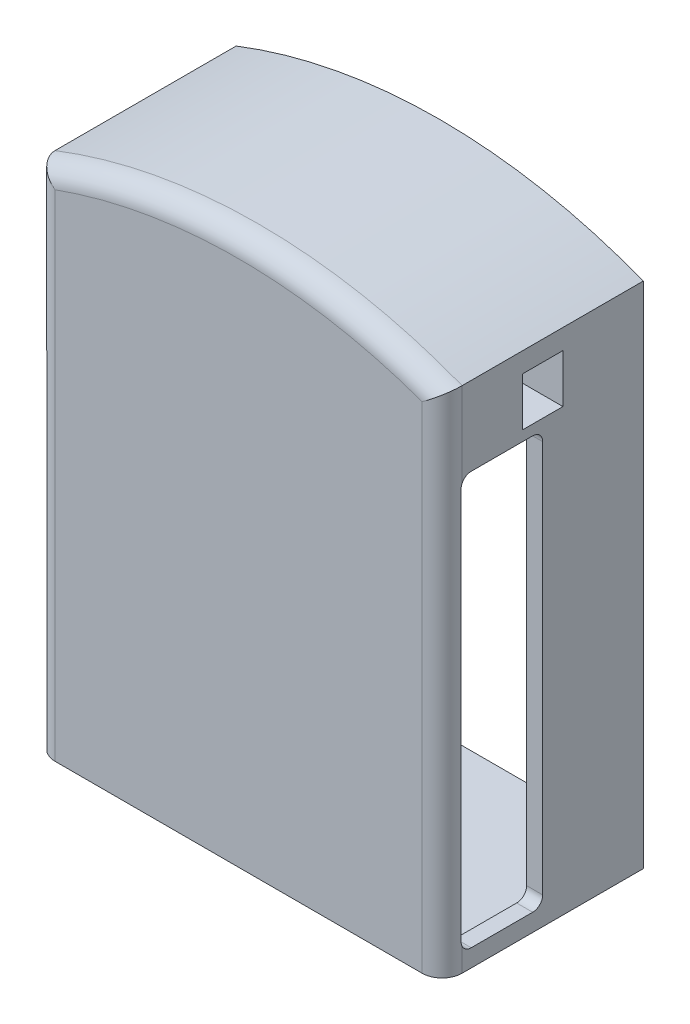
SolidWorks part; units mm, degrees
ref_plane "Front Plane" through (0, 0, 0) normal (0, 0, 1) x (1, 0, 0)
ref_plane "Top Plane" through (0, 0, 0) normal (0, 1, 0) x (1, 0, 0)
ref_plane "Right Plane" through (0, 0, 0) normal (1, 0, 0) x (0, 0, -1)
sketch "Sketch1" plane through (0, 0, 0) normal (0, 1, 0) x (1, 0, 0)
  line L1 (-50.8, -25.1) -> (50.8, -25.1)
  line L2 (-50.8, -25.1) -> (-50.8, 25.1)
  line L3 (-50.8, 25.1) -> (50.8, 25.1)
  line L4 (50.8, -25.1) -> (50.8, 25.1)
  point P4 (0, 25.1)
  point P6 (50.8, 0)
  dimension "D1" = 50.2
  dimension "D2" = 101.6
extrude "Boss-Extrude1" add sketch "Sketch1" along normal blind 127
shell "Shell2" thickness 4
sketch "Sketch2" plane through (0, 0, 21.1) normal (0, 0, -1) x (-1, 0, 0)
  line L2 (40.0386, 104.4679) -> (-40.0386, 104.4679)
  line L3 (41.5386, 12.0015) -> (41.5386, 105.9679)
  line L6 (-40.0386, 13.5015) -> (-40.0386, 104.4679)
  line L8 (40.0386, 13.5015) -> (40.0386, 104.4679)
  line L9 (-41.5386, 12.0015) -> (-41.5386, 105.9679)
  line L10 (-41.5386, 12.0015) -> (-41.5386, 4)
  line L11 (-46.8, 4) -> (46.8, 4) construction
  line L12 (-40.0386, 13.5015) -> (-40.0386, 4)
  line L13 (40.0386, 13.5015) -> (40.0386, 4)
  line L14 (46.8, 4) -> (-46.8, 4) construction
  line L15 (41.5386, 12.0015) -> (41.5386, 4)
  line L16 (41.5386, 4) -> (40.0386, 4)
  line L17 (-41.5386, 4) -> (-40.0386, 4)
  line L18 (-41.5386, 105.9679) -> (41.5386, 105.9679)
  line L19 (-41.5386, 12.0015) -> (41.5386, 12.0015) construction
  line L20 (-40.0386, 13.5015) -> (40.0386, 13.5015) construction
  line L22 (-41.5386, 12.0015) -> (-41.5386, 115.4679) construction
  line L23 (-40.0386, 13.5015) -> (-40.0386, 113.9679) construction
  line L24 (-40.0386, 113.9679) -> (40.0386, 113.9679) construction
  line L25 (-41.5386, 115.4679) -> (41.5386, 115.4679) construction
  line L26 (41.5386, 12.0015) -> (41.5386, 115.4679) construction
  line L27 (40.0386, 13.5015) -> (40.0386, 113.9679) construction
  point P9 (0, 63.5)
  point P12 (0, 63.5)
  point P15 (0, 113.9679)
  point P18 (-40.0386, 63.7347)
  dimension "D3" = 1.5
  dimension "D1" = 1.5
extrude "Boss-Extrude2" add sketch "Sketch2" along normal blind 2
fillet "Fillet1" radius 5 2 edges at (50.8, 63.5, 25.1) (-50.8, 63.5, 25.1)
sketch "Sketch4" plane through (50.8, 0, 0) normal (1, 0, 0) x (0, 0, -1)
  line L5 (-20.3461, 4.3823) -> (0, 4.3823)
  line L6 (-20.3461, 4.3823) -> (-20.3461, 107.3452)
  line L7 (-20.3461, 107.3452) -> (0, 107.3452)
  line L8 (0, 4.3823) -> (0, 107.3452)
extrude "Cut-Extrude2" cut sketch "Sketch4" against normal blind 7
fillet "Fillet2" radius 2.5 4 edges at (48.797, 4.3823, 20.3461) (48.8, 4.3823, 0) (48.8, 107.3452, 0) (48.797, 107.3452, 20.3461)
mirror "Mirror1" about plane through (0, 0, 0) normal (1, 0, 0) of "Fillet2", "Cut-Extrude2"
sketch "Sketch5" plane through (0, 0, 25.1) normal (0, 0, 1) x (1, 0, 0)
  line L0 (-50.8, 127) -> (50.8, 127)
  arc A0 (-50.8, 127) -> (50.8, 127) centre (0, -3.4583) cw
  dimension "D1" = 140
extrude "Boss-Extrude4" add sketch "Sketch5" against normal blind 50.2
fillet "Fillet4" radius 5 1 edges at (0, 136.5417, 25.1)
sketch "Sketch6" plane through (46.8, 0, 0) normal (-1, 0, 0) x (0, 0, 1)
  line L0 (-25.1, 120.6928) -> (25.1, 120.6928) construction
  line L1 (0, -55.88) -> (0, 55.88) construction
  line L2 (25.1, 0) -> (25.1, 123.5353) construction
  line L3 (21.1, 123) -> (-25.1, 123) construction
  line L4 (-5.05, 122) -> (5.05, 122)
  line L5 (-5.05, 122) -> (-5.05, 109.9)
  line L6 (-5.05, 109.9) -> (5.05, 109.9)
  line L7 (5.05, 122) -> (5.05, 109.9)
  line L8 (-6.05, 123) -> (6.05, 123)
  line L9 (6.05, 123) -> (6.05, 108.9)
  line L10 (-6.05, 108.9) -> (6.05, 108.9)
  line L11 (-6.05, 123) -> (-6.05, 108.9)
  point P3 (0, 120.6928)
  point P9 (0, 122)
  point P12 (0, 0)
  dimension "D1" = 10.1
  dimension "D2" = 12.1
  dimension "D3" = 1
  dimension "D4" = 1
extrude "Boss-Extrude5" add sketch "Sketch6" along normal blind 9
sketch "Sketch7" plane through (46.8, 0, 0) normal (-1, 0, 0) x (0, 0, 1)
  line L4 (-5.05, 122) -> (-5.05, 109.9)
  line L5 (-5.05, 109.9) -> (5.05, 109.9)
  line L6 (5.05, 109.9) -> (5.05, 122)
  line L7 (5.05, 122) -> (-5.05, 122)
  line L8 (-5.05, 122) -> (-5.05, 109.9)
  line L9 (-5.05, 109.9) -> (5.05, 109.9)
  line L10 (5.05, 109.9) -> (5.05, 122)
  line L11 (5.05, 122) -> (-5.05, 122)
  dimension "D1" = 0
extrude "Cut-Extrude3" cut sketch "Sketch7" against normal blind 9
mirror "Mirror2" about plane through (0, 0, 0) normal (1, 0, 0) of "Cut-Extrude3", "Boss-Extrude5"
